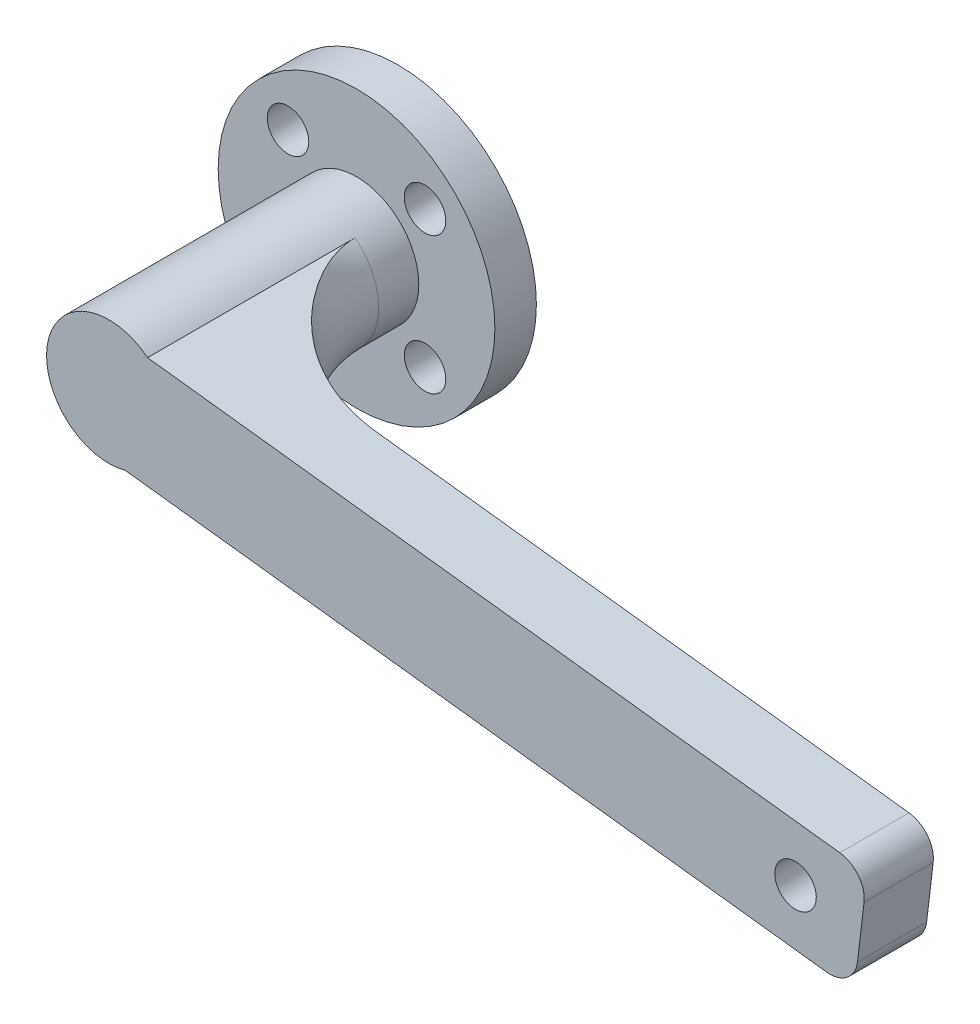
SolidWorks part; units mm, degrees
ref_plane "前视基准面" through (0, 0, 0) normal (0, 0, 1) x (1, 0, 0)
ref_plane "上视基准面" through (0, 0, 0) normal (0, 1, 0) x (1, 0, 0)
ref_plane "右视基准面" through (0, 0, 0) normal (1, 0, 0) x (0, 0, -1)
sketch "草图1" plane through (0, 0, 0) normal (0, 0, 1) x (1, 0, 0)
  circle A0 centre (0, 0) radius 10
  dimension "D1" = 20
extrude "凸台-拉伸1" add sketch "草图1" along normal blind 3
sketch "草图2" plane through (0, 0, 3) normal (0, 0, 1) x (1, 0, 0)
  line L1 (4.95, -4.95) -> (-4.95, -4.95)
  line L2 (4.95, -4.95) -> (4.95, 4.95)
  line L3 (4.95, 4.95) -> (-4.95, 4.95)
  line L4 (-4.95, -4.95) -> (-4.95, 4.95)
  line L5 (4.95, -4.95) -> (-4.95, 4.95) construction
  line L6 (4.95, 4.95) -> (-4.95, -4.95) construction
  circle A0 centre (0, 0) radius 1.5
  circle A2 centre (4.95, 4.95) radius 1.5
  circle A3 centre (-4.95, 4.95) radius 1.5
  circle A4 centre (-4.95, -4.95) radius 1.5
  circle A5 centre (4.95, -4.95) radius 1.5
  dimension "D1" = 3
  dimension "D2" = 9.9
  dimension "D4" = 3
  dimension "D3" = 9.9
extrude "切除-拉伸1" cut sketch "草图2" against normal through all contours L3 A3 L4 | L4 A3 L3 | L2 A2 L3 | L3 A2 L2 | L4 A4 L1 | L1 A4 L4 | L1 A5 L2 | L2 A5 L1 | A0 region at (-5.1622, -5.1622, 3) region at (-4.3134, -4.3134, 3) region at (4.3134, -4.3134, 3) region at (5.1622, -5.1622, 3) region at (-5.1622, 5.1622, 3) region at (-4.3134, 4.3134, 3) region at (4.3134, 4.3134, 3) region at (5.1622, 5.1622, 3)
sketch "草图3" plane through (0, 0, 3) normal (0, 0, 1) x (1, 0, 0)
  circle A0 centre (0, 0) radius 4.5
  circle A1 centre (-4.95, 4.95) radius 1.5 construction
  circle A2 centre (0, 0) radius 10
  circle A3 centre (0, 0) radius 10
  circle A4 centre (-4.95, 4.95) radius 1.5
  point P2 (0.0228, 0)
  circle M5 centre (0, 0) radius 1.5
  dimension "D1" = 0
  dimension "D2" = 9
extrude "凸台-拉伸2" add sketch "草图3" along normal blind 12.9 contours A0 M5 region at (-4.3727, 0, 3)
sketch "草图4" plane through (0, 0, 0) normal (0, 0, -1) x (-1, 0, 0)
  circle A0 centre (0, 0) radius 1.5 construction
  circle A3 centre (0, 0) radius 1.5
extrude "凸台-拉伸4" add sketch "草图4" against normal up to surface (15.9 mm away) up to face at (1.5, 0, 15.9)
sketch "草图5" plane through (0, 0, 15.9) normal (0, 0, 1) x (1, 0, 0)
  line L0 (-0.2722, -0.1379) -> (54.3398, -6.6595) construction
  line L1 (54.8141, -2.6877) -> (53.8655, -10.6312)
  line L2 (53.8655, -10.6312) -> (-0.7465, -4.1097)
  line L3 (-0.7465, -4.1097) -> (0.2021, 3.8339)
  line L4 (54.8141, -2.6877) -> (0.2021, 3.8339)
  dimension "D1" = 55
  dimension "D2" = 4
extrude "凸台-拉伸5" add sketch "草图5" along normal blind 5
sketch "草图6" plane through (0, 0, 20.9) normal (0, 0, 1) x (1, 0, 0)
  line L0 (54.3398, -6.6595) -> (49.6269, -6.0967) construction
  line L1 (53.8655, -10.6312) -> (54.8141, -2.6877) construction
  line L2 (54.8141, -2.6877) -> (0.2021, 3.8339) construction
  circle A0 centre (49.6269, -6.0967) radius 1.5
  circle A1 centre (0, 0) radius 4.5 construction
  point P7 (0, 0)
  point P8 (69.3733, -9.3461)
  dimension "D1" = 3
  dimension "D2" = 50
extrude "切除-拉伸2" cut sketch "草图6" against normal through all
sketch "草图7" plane through (0, 0, 15.9) normal (0, 0, 1) x (1, 0, 0)
  line L3 (0.2021, 3.8339) -> (2.7987, 3.5238)
  line L4 (1.1871, -4.3406) -> (-0.7465, -4.1097)
  line L5 (-0.7465, -4.1097) -> (0.2021, 3.8339)
  line L6 (0.2021, 3.8339) -> (2.7987, 3.5238)
  line L7 (1.1871, -4.3406) -> (-0.7465, -4.1097)
  line L8 (-0.7465, -4.1097) -> (0.2021, 3.8339)
  arc A1 (2.7987, 3.5238) -> (1.1871, -4.3406) centre (0, 0) ccw
  arc A2 (2.7987, 3.5238) -> (1.1871, -4.3406) centre (0, 0) ccw
  dimension "D1" = 0
extrude "凸台-拉伸8" add sketch "草图7" along normal blind 5 contours L6 A2 L7 L8
fillet "圆角1" radius 10 1 edges at (4.4084, -0.9034, 15.9)
fillet "圆角2" radius 2 2 edges at (53.8655, -10.6312, 18.4) (54.8141, -2.6877, 18.4)
sketch "草图8" plane through (0, 0, 0) normal (0, 0, -1) x (-1, 0, 0)
  circle A0 centre (0, 0) radius 2.5
  dimension "D1" = 5
extrude "切除-拉伸3" cut sketch "草图8" against normal blind 3
